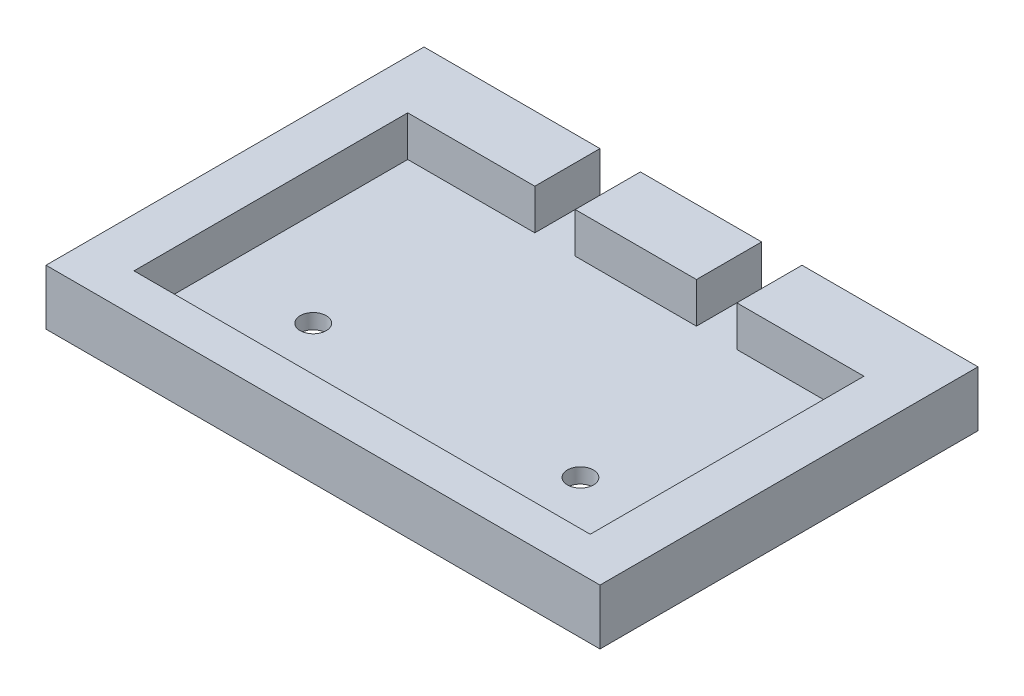
SolidWorks part; units mm, degrees
ref_plane "Front Plane" through (0, 0, 0) normal (0, 0, 1) x (1, 0, 0)
ref_plane "Top Plane" through (0, 0, 0) normal (0, 1, 0) x (1, 0, 0)
ref_plane "Right Plane" through (0, 0, 0) normal (1, 0, 0) x (0, 0, -1)
sketch "Sketch1" plane through (0, 0, 0) normal (0, 1, 0) x (1, 0, 0)
  line L1 (45.5, -35) -> (-45.5, -35)
  line L2 (45.5, -35) -> (45.5, 35)
  line L3 (45.5, 35) -> (-45.5, 35)
  line L4 (-45.5, -35) -> (-45.5, 35)
  line L5 (45.5, -35) -> (-45.5, 35) construction
  line L6 (45.5, 35) -> (-45.5, -35) construction
  point P0 (0, 0)
  dimension "D1" = 91
  dimension "D2" = 70
extrude "Boss-Extrude1" add sketch "Sketch1" along normal blind 12
sketch "Sketch2" plane through (0, 12, 0) normal (0, 1, 0) x (1, 0, 0)
  line L0 (-45.5, 35) -> (-45.5, -35) construction
  line L1 (45.5, -35) -> (45.5, 35) construction
  line L2 (-45.5, -35) -> (45.5, -35) construction
  circle A0 centre (-20.5, -4) radius 2
  circle A1 centre (20.5, -4) radius 2
  point P0 (-20.5, -4)
  point P1 (20.5, -4)
  dimension "D4" = 4
  dimension "D1" = 25
  dimension "D2" = 25
  dimension "D3" = 31
extrude "Cut-Extrude1" cut sketch "Sketch2" against normal through all
sketch "Sketch4" plane through (0, 0, -35) normal (0, 0, -1) x (-1, 0, 0)
  line L0 (-45.5, 12) -> (-45.5, 0) construction
  line L1 (-15.5, 12) -> (-9.3, 12)
  line L2 (-15.5, 12) -> (-15.5, 5.8)
  line L3 (-15.5, 5.8) -> (-9.3, 5.8)
  line L4 (-9.3, 12) -> (-9.3, 5.8)
  line L5 (9.3, 12) -> (15.5, 12)
  line L6 (9.3, 12) -> (9.3, 5.8)
  line L7 (9.3, 5.8) -> (15.5, 5.8)
  line L8 (15.5, 12) -> (15.5, 5.8)
  line L9 (45.5, 12) -> (45.5, 0) construction
  line L10 (-45.5, 12) -> (45.5, 12) construction
  dimension "D1" = 6.2
  dimension "D2" = 30
  dimension "D3" = 30
extrude "Cut-Extrude2" cut sketch "Sketch4" against normal blind 15
sketch "Sketch5" plane through (0, 12, 0) normal (0, 1, 0) x (1, 0, 0)
  line L0 (0, 0) -> (0, 35) construction
  line L5 (9.3, 35) -> (-9.3, 35) construction
  line L10 (-35, 25) -> (35, 25)
  line L11 (-35, 25) -> (-35, -17)
  line L12 (-35, -17) -> (35, -17)
  line L13 (35, 25) -> (35, -17)
  dimension "D1" = 70
  dimension "D2" = 25
  dimension "D3" = 42
extrude "Cut-Extrude3" cut sketch "Sketch5" against normal up to surface (6.2 mm away) up to face at (-12.4, 5.8, -27.5)
sketch "Sketch6" plane through (0, 12, 0) normal (0, 1, 0) x (1, 0, 0)
  line L0 (-45.5, 35) -> (-45.5, -35) construction
  line L1 (-42.5, 42.1667) -> (42.5, 42.1667)
  line L2 (-42.5, 42.1667) -> (-42.5, -33)
  line L3 (-42.5, -33) -> (42.5, -33)
  line L4 (42.5, 42.1667) -> (42.5, -33)
  line L5 (-56.1126, 52.7895) -> (52.9689, 52.7895)
  line L6 (-56.1126, 52.7895) -> (-56.1126, -44.638)
  line L7 (-56.1126, -44.638) -> (52.9689, -44.638)
  line L8 (52.9689, 52.7895) -> (52.9689, -44.638)
  line L9 (45.5, -35) -> (45.5, 35) construction
  line L10 (-45.5, -35) -> (45.5, -35) construction
  dimension "D1" = 3
  dimension "D2" = 3
  dimension "D3" = 2
extrude "Cut-Extrude4" cut sketch "Sketch6" against normal blind 28
sketch "Sketch7" plane through (0, 0, -35) normal (0, 0, -1) x (-1, 0, 0)
  line L0 (42.5, 12) -> (42.5, 0) construction
  line L1 (-42.5, 0) -> (42.5, 0)
  line L2 (-42.5, 0) -> (-42.5, 3.5)
  line L3 (-42.5, 3.5) -> (42.5, 3.5)
  line L4 (42.5, 0) -> (42.5, 3.5)
  dimension "D1" = 3.5
extrude "Cut-Extrude5" cut sketch "Sketch7" against normal through all
fillet "Fillet3" radius 10 1 edges at (0, 3.5, 33)
sketch "Sketch8" plane through (0, 12, 0) normal (0, 1, 0) x (1, 0, 0)
  line L0 (42.5, -33) -> (42.5, 35) construction
  line L1 (-42.5, -33) -> (42.5, -33)
  line L2 (-42.5, -33) -> (-42.5, -23)
  line L3 (-42.5, -23) -> (42.5, -23)
  line L4 (42.5, -33) -> (42.5, -23)
  dimension "D1" = 10
extrude "Cut-Extrude7" cut sketch "Sketch8" against normal blind 17
